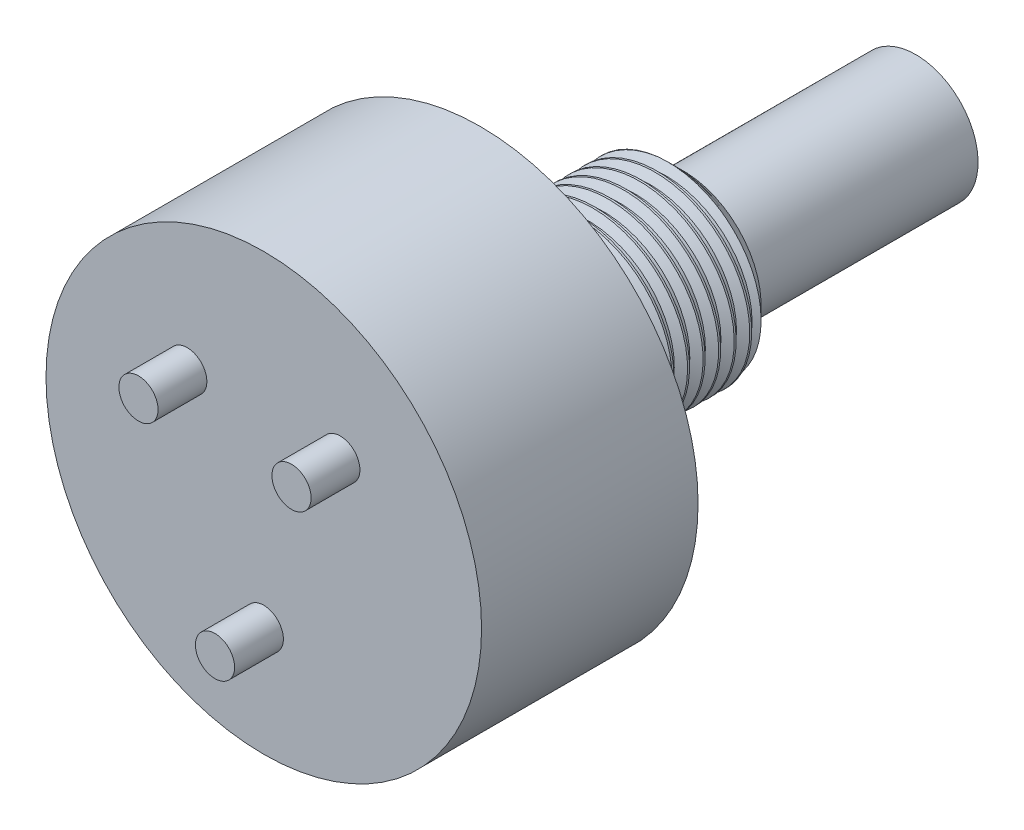
SolidWorks part; units mm, degrees
ref_plane "Front Plane" through (0, 0, 0) normal (0, 0, 1) x (1, 0, 0)
ref_plane "Top Plane" through (0, 0, 0) normal (0, 1, 0) x (1, 0, 0)
ref_plane "Right Plane" through (0, 0, 0) normal (1, 0, 0) x (0, 0, -1)
sketch "Sketch1" plane through (0, 0, 0) normal (1, 0, 0) x (0, 0, -1)
  line L0 (0, 0) -> (-34.4491, 0) construction
  line L1 (0, 11.115) -> (-11.05, 11.115)
  line L2 (-11.05, 11.115) -> (-11.05, 0)
  line L3 (-11.05, 0) -> (22.23, 0)
  line L4 (22.23, 0) -> (22.23, 3.175)
  line L5 (22.23, 3.175) -> (10.37, 3.175)
  line L6 (10.37, 3.175) -> (10.37, 4.7625)
  line L7 (10.37, 4.7625) -> (1.5, 4.7625)
  line L8 (1.5, 4.7625) -> (1.5, 5.15)
  line L9 (1.5, 5.15) -> (0, 5.15)
  line L10 (0, 5.15) -> (0, 11.115)
  dimension "D1" = 22.23
  dimension "D2" = 11.05
  dimension "D3" = 1.5
  dimension "D4" = 10.3
  dimension "D5" = 9.525
  dimension "D6" = 6.35
  dimension "D7" = 10.37
  dimension "D8" = 22.23
revolve "Revolve1" add sketch "Sketch1" angle 360 about L0
sketch "Sketch2" plane through (0, 0, 11.05) normal (0, 0, 1) x (1, 0, 0)
  circle A0 centre (0, -5.525) radius 1
  circle A1 centre (-3.905, 3.9085) radius 1
  circle A2 centre (3.905, 3.9085) radius 1
  circle A3 centre (0, 0) radius 5.525 construction
  dimension "D2" = 11.05
  dimension "D3" = 2
  dimension "D1" = 7.81
extrude "Boss-Extrude1" add sketch "Sketch2" along normal offset from surface (2.49 mm away) 13.54 up to face at (-11.115, 0, 0)
sketch "Sketch3" plane through (0, 0, 0) normal (0, 0, -1) x (-1, 0, 0)
  circle A0 centre (0, -7.37) radius 0.785
  dimension "D1" = 1.57
  dimension "D2" = 7.37
extrude "Boss-Extrude2" add sketch "Sketch3" along normal blind 1.57
chamfer "Chamfer1" distance 0.8 angle 45 1 edges at (-4.7625, 0, -10.37)
thread "Thread1" pitch 0.7937 method cut trim with start face yes trim with end face yes profile "Thread Profile1" start angle 0, offset 1, length 0, pitch 0.7937, diameter 9.525
ref_plane "Plane1" through (4.7625, 0, -11.37) normal (0, -1, 0) x (1, 0, 0)
sketch "Thread Profile1" plane through (4.7625, 0, -11.37) normal (0, -1, 0) x (1, 0, 0)
  line L0 (0, 0) -> (0, 0.7937) construction
  line L11 (0, 0) -> (0, 0.6945)
  line L12 (0, 0.6945) -> (-0.4296, 0.4465)
  line L13 (-0.4296, 0.4465) -> (-0.4296, 0.248)
  line L15 (-0.4296, 0.248) -> (0, 0)
  line L17 (-0.4296, 0.3473) -> (0, 0.3473) construction
  point P2 (0, 0)
  dimension "Pitch" = 0.7937
  dimension "Profile_Angle" = 60
  dimension "Profile_Land" = 0.1984
  dimension "Profile_Height" = 0.4296
sketch "Sketch8" plane through (0, 0, -22.23) normal (0, 0, -1) x (-1, 0, 0)
  line L0 (-2.1729, -2.315) -> (2.1729, -2.315)
  circle A0 centre (0, 0) radius 3.175 construction
  arc A1 (2.1729, -2.315) -> (-2.1729, -2.315) centre (0, 0) cw
  point P5 (0, 3.175)
  dimension "D1" = 5.49
extrude "Cut-Extrude1" cut sketch "Sketch8" against normal blind 9
